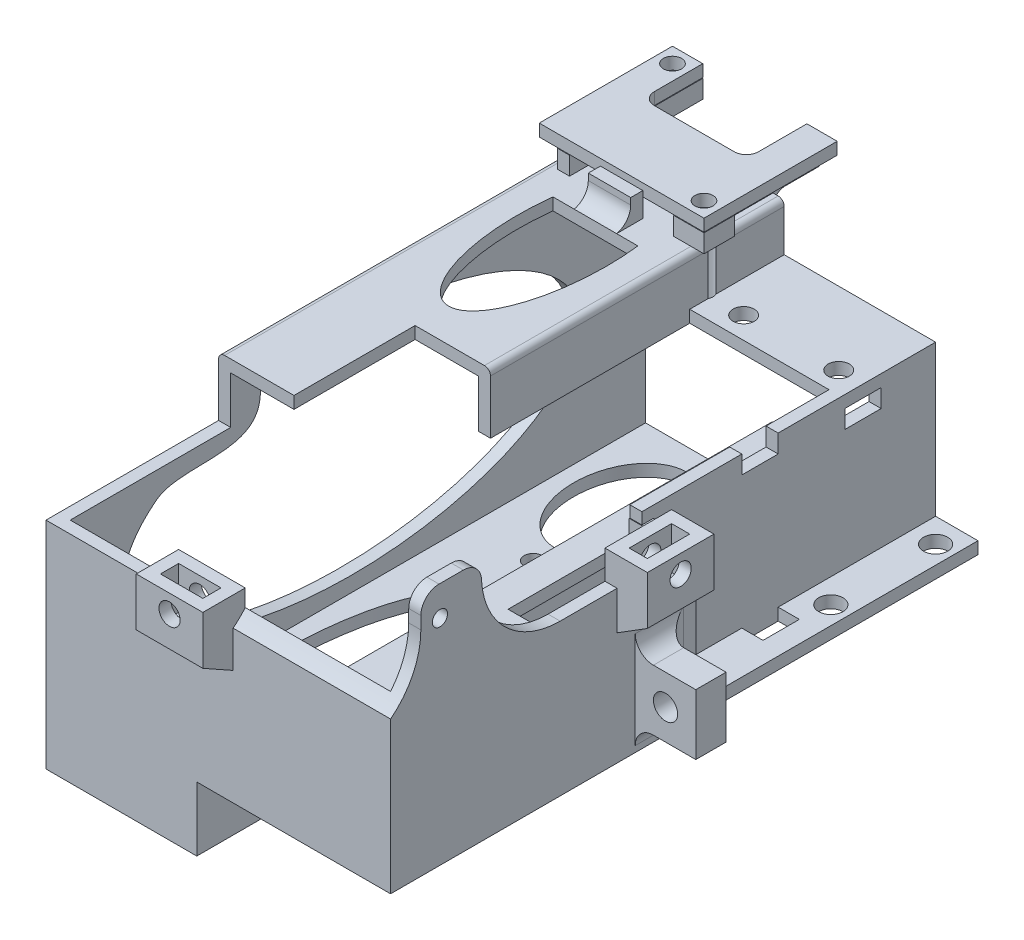
SolidWorks part; units mm, degrees
ref_plane "Front Plane" through (0, 0, 0) normal (0, 0, 1) x (1, 0, 0)
ref_plane "Top Plane" through (0, 0, 0) normal (0, 1, 0) x (1, 0, 0)
ref_plane "Right Plane" through (0, 0, 0) normal (1, 0, 0) x (0, 0, -1)
sketch "Sketch1" plane through (0, 0, 0) normal (0, 1, 0) x (1, 0, 0)
  line L1 (26.45, 47.5) -> (-26.45, 47.5)
  line L2 (26.45, 47.5) -> (26.45, -47.5)
  line L3 (26.45, -47.5) -> (-26.45, -47.5)
  line L4 (-26.45, 47.5) -> (-26.45, -47.5)
  line L5 (26.45, 47.5) -> (-26.45, -47.5) construction
  line L6 (26.45, -47.5) -> (-26.45, 47.5) construction
  point P0 (0, 0)
  dimension "D1" = 52.9
  dimension "D2" = 95
extrude "Boss-Extrude1" add sketch "Sketch1" along normal blind 2
sketch "Sketch2" plane through (0, 2, 0) normal (0, 1, 0) x (1, 0, 0)
  line L0 (-26.45, -47.5) -> (26.45, -47.5)
  line L1 (26.45, -47.5) -> (26.45, 47.5) construction
  line L2 (26.45, -47.5) -> (26.45, -1.1)
  line L3 (26.45, -1.1) -> (19.45, -1.1)
  line L4 (19.45, -1.1) -> (19.45, 47.5)
  line L5 (26.45, 47.5) -> (-26.45, 47.5) construction
  line L6 (19.45, 47.5) -> (-26.45, 47.5) construction
  line L7 (-26.45, 47.5) -> (-26.45, -47.5)
  line L8 (-28.45, 49.5) -> (-28.45, -49.5) construction
  line L9 (-28.45, -49.5) -> (28.45, -49.5)
  line L10 (28.45, -49.5) -> (28.45, 0.9)
  line L11 (28.45, 0.9) -> (21.45, 0.9)
  line L12 (21.45, 0.9) -> (21.45, 49.5) construction
  line L13 (21.45, 49.5) -> (-28.45, 49.5) construction
  line L14 (19.45, 47.5) -> (21.45, 47.5)
  line L15 (-26.45, 47.5) -> (-28.45, 47.5)
  line L16 (-28.45, -49.5) -> (-28.45, 47.5)
  line L17 (21.45, 0.9) -> (21.45, 47.5)
  dimension "D1" = 46.4
  dimension "D2" = 7
  dimension "D3" = 2
extrude "Boss-Extrude2" add sketch "Sketch2" along normal blind 25 from offset 2 offset against normal yes
sketch "Sketch4" plane through (0, 25, 0) normal (0, 1, 0) x (1, 0, 0)
  line L0 (19.45, -1.1) -> (-28.45, -1) construction
  line L1 (-28.45, 47.5) -> (-28.45, -49.5) construction
  line L3 (-28.45, -1) -> (-26.45, -1)
  line L4 (-28.45, -1) -> (-28.45, 47.5)
  line L5 (-28.45, 47.5) -> (-26.45, 47.5)
  line L6 (-26.45, -1) -> (-26.45, 47.5)
extrude "Boss-Extrude3" add sketch "Sketch4" along normal blind 9.8
sketch "Sketch6" plane through (-26.45, 0, 0) normal (1, 0, 0) x (0, 0, -1)
  line L0 (47.5, 34.8) -> (47.5, 2) construction
  line L1 (-1, 34.8) -> (47.5, 34.8)
  line L2 (-1, 34.8) -> (-1, 32.8)
  line L3 (-1, 32.8) -> (47.5, 32.8)
  line L4 (47.5, 34.8) -> (47.5, 32.8)
  dimension "D1" = 2
extrude "Boss-Extrude4" add sketch "Sketch6" along normal blind 22.9
sketch "Sketch7" plane through (0, 32.8, 0) normal (0, -1, 0) x (1, 0, 0)
  line L0 (-3.55, 1) -> (-26.45, 1) construction
  line L1 (-3.55, -47.5) -> (-5.55, -47.5)
  line L2 (-3.55, -47.5) -> (-3.55, 1)
  line L3 (-3.55, 1) -> (-5.55, 1)
  line L4 (-5.55, -47.5) -> (-5.55, 1)
  dimension "D1" = 2
extrude "Boss-Extrude5" add sketch "Sketch7" along normal blind 7.9
sketch "Sketch8" plane through (-3.55, 0, 0) normal (1, 0, 0) x (0, 0, -1)
  line L0 (47.5, 24.9) -> (47.5, 34.8) construction
  line L1 (-1, 24.9) -> (47.5, 24.9)
  line L2 (-1, 24.9) -> (-1, 26.9)
  line L3 (-1, 26.9) -> (47.5, 26.9)
  line L4 (47.5, 24.9) -> (47.5, 26.9)
  dimension "D1" = 2
extrude "Boss-Extrude6" add sketch "Sketch8" along normal up to surface (25 mm away) up to face at (21.45, 13.5, -24.2)
sketch "Sketch9" plane through (0, 0, 1) normal (0, 0, 1) x (1, 0, 0)
  line L0 (-28.45, 25) -> (-26.45, 25)
  line L1 (-26.45, 25) -> (-26.45, 32.8)
  line L2 (-26.45, 32.8) -> (-16, 32.8)
  line L3 (-5.55, 32.8) -> (-26.45, 32.8) construction
  line L4 (-16, 32.8) -> (-16, 34.8)
  line L5 (-28.45, 34.8) -> (-3.55, 34.8) construction
  line L6 (-16, 34.8) -> (-28.45, 34.8)
  line L7 (-28.45, 34.8) -> (-28.45, 25)
extrude "Boss-Extrude7" add sketch "Sketch9" along normal blind 20
sketch "Sketch3" plane through (0, 2, 0) normal (0, 1, 0) x (1, 0, 0)
  line L0 (19.45, -1.1) -> (-26.45, -1.1) construction
  line L2 (-26.45, 47.5) -> (-26.45, -47.5) construction
  line L3 (19.45, -1.1) -> (-0.55, -1.1)
  line L4 (-0.55, -1.1) -> (-0.55, 31.9)
  line L5 (-0.55, 31.9) -> (19.45, 31.9)
  line L6 (19.45, 47.5) -> (19.45, -1.1) construction
  line L7 (19.45, 31.9) -> (19.45, -1.1)
  dimension "D1" = 20
  dimension "D2" = 33
extrude "Cut-Extrude1" cut sketch "Sketch3" against normal mid plane 55
sketch "Sketch62" plane through (-0.55, 0, 0) normal (1, 0, 0) x (0, 0, -1)
  line L1 (-1, 26.9) -> (31.9, 26.9)
  line L2 (-1, 26.9) -> (-1, 24.9)
  line L3 (-1, 24.9) -> (31.9, 24.9)
  line L4 (31.9, 26.9) -> (31.9, 24.9)
extrude "Cut-Extrude25" cut sketch "Sketch62" against normal up to surface (3 mm away) up to face at (-3.55, 30.85, -23.25)
sketch "Sketch13" plane through (0, 25, 0) normal (0, 1, 0) x (1, 0, 0)
  line L0 (28.45, -49.5) -> (28.45, 0.9) construction
  line L1 (26.45, -1.1) -> (28.45, -1.1)
  line L2 (26.45, -1.1) -> (26.45, -12.1)
  line L3 (26.45, -12.1) -> (28.45, -12.1)
  line L4 (28.45, -1.1) -> (28.45, -12.1)
  dimension "D1" = 11
extrude "Boss-Extrude10" add sketch "Sketch13" along normal blind 8 from offset 3.25 offset against normal yes
sketch "Sketch14" plane through (28.45, 0, 0) normal (1, 0, 0) x (0, 0, -1)
  line L1 (-12.1, 29.75) -> (-1.1, 29.75)
  line L2 (-12.1, 29.75) -> (-12.1, 21.75)
  line L3 (-12.1, 21.75) -> (-1.1, 21.75)
  line L4 (-1.1, 29.75) -> (-1.1, 21.75)
  dimension "D1" = 8
extrude "Boss-Extrude11" add sketch "Sketch14" along normal blind 5
sketch "Sketch15" plane through (0, 29.75, 0) normal (0, 1, 0) x (1, 0, 0)
  line L1 (28.45, -10.1) -> (31.45, -10.1)
  line L2 (28.45, -10.1) -> (28.45, -3.1)
  line L3 (28.45, -3.1) -> (31.45, -3.1)
  line L4 (31.45, -10.1) -> (31.45, -3.1)
  line L6 (26.45, -1.1) -> (26.45, -12.1) construction
  line L7 (26.45, -12.1) -> (33.45, -12.1) construction
  line L8 (33.45, -1.1) -> (26.45, -1.1) construction
  dimension "D1" = 2
  dimension "D2" = 3
  dimension "D3" = 2
  dimension "D4" = 2
extrude "Cut-Extrude2" cut sketch "Sketch15" against normal blind 6
sketch "Sketch16" plane through (28.45, 0, 0) normal (1, 0, 0) x (0, 0, -1)
  line L0 (-6.6, 29.75) -> (-6.6, 23.75) construction
  line L1 (-3.1, 29.75) -> (-10.1, 29.75) construction
  line L2 (-3.1, 23.75) -> (-10.1, 23.75) construction
  circle A0 centre (-6.6, 26.75) radius 1.75
  dimension "D1" = 3.5
extrude "Cut-Extrude3" cut sketch "Sketch16" against normal mid plane 15
sketch "Sketch30" plane through (0, 0, 12.1) normal (0, 0, 1) x (1, 0, 0)
  line L0 (33.45, 21.75) -> (26.6464, 17.5043)
rib "Rib8" sketch "Sketch30" sketch "Sketch30" thickness 11 extrusion direction parallel to sketch draft on no parameters "D1"=11
sketch "Sketch37" plane through (0, 23.75, 0) normal (0, 1, 0) x (1, 0, 0)
  line L4 (28.45, -3.1) -> (28.45, -10.1)
  line L5 (28.45, -10.1) -> (31.45, -10.1)
  line L6 (31.45, -10.1) -> (31.45, -3.1)
  line L7 (31.45, -3.1) -> (28.45, -3.1)
  line L8 (28.45, -3.1) -> (28.45, -10.1)
  line L9 (28.45, -10.1) -> (31.45, -10.1)
  line L10 (31.45, -10.1) -> (31.45, -3.1)
  line L11 (31.45, -3.1) -> (28.45, -3.1)
  dimension "D1" = 0
extrude "Cut-Extrude9" cut sketch "Sketch37" against normal blind 1
sketch "Sketch12" plane through (0, 25, 0) normal (0, 1, 0) x (1, 0, 0)
  line L0 (28.45, -49.5) -> (-8.55, -49.5) construction
  line L1 (-28.45, -49.5) -> (28.45, -49.5) construction
  line L2 (26.45, -47.5) -> (-26.45, -47.5) construction
  line L3 (-8.55, -49.5) -> (2.45, -49.5)
  line L4 (-8.55, -49.5) -> (-8.55, -47.5)
  line L5 (-8.55, -47.5) -> (2.45, -47.5)
  line L6 (2.45, -49.5) -> (2.45, -47.5)
  dimension "D1" = 37
  dimension "D2" = 11
extrude "Boss-Extrude9" add sketch "Sketch12" along normal blind 8 from offset 3.25 offset against normal yes
sketch "Sketch18" plane through (0, 0, 49.5) normal (0, 0, 1) x (1, 0, 0)
  line L1 (-8.55, 29.75) -> (2.45, 29.75)
  line L2 (-8.55, 29.75) -> (-8.55, 21.75)
  line L3 (-8.55, 21.75) -> (2.45, 21.75)
  line L4 (2.45, 29.75) -> (2.45, 21.75)
  dimension "D1" = 8
  dimension "D2" = 11
extrude "Boss-Extrude12" add sketch "Sketch18" along normal blind 5
sketch "Sketch20" plane through (0, 29.75, 0) normal (0, 1, 0) x (1, 0, 0)
  line L0 (-3.05, -47.5) -> (-3.05, -54.5) construction
  line L1 (2.45, -47.5) -> (-8.55, -47.5) construction
  line L2 (2.45, -54.5) -> (-8.55, -54.5) construction
  line L3 (2.45, -54.5) -> (2.45, -47.5) construction
  line L4 (0.45, -52.5) -> (-6.55, -52.5)
  line L5 (0.45, -52.5) -> (0.45, -49.5)
  line L6 (0.45, -49.5) -> (-6.55, -49.5)
  line L7 (-6.55, -52.5) -> (-6.55, -49.5)
  line L8 (0.45, -52.5) -> (-6.55, -49.5) construction
  line L9 (0.45, -49.5) -> (-6.55, -52.5) construction
  point P6 (-3.05, -51)
  point P13 (2.45, -51)
  dimension "D1" = 2
  dimension "D2" = 2
extrude "Cut-Extrude4" cut sketch "Sketch20" against normal blind 6
sketch "Sketch21" plane through (0, 0, 49.5) normal (0, 0, 1) x (1, 0, 0)
  line L0 (-3.05, 29.75) -> (-3.05, 23.75) construction
  line L1 (0.45, 29.75) -> (-6.55, 29.75) construction
  line L2 (0.45, 23.75) -> (-6.55, 23.75) construction
  circle A0 centre (-3.05, 26.75) radius 1.75
  dimension "D1" = 3.5
extrude "Cut-Extrude5" cut sketch "Sketch21" against normal mid plane 20
sketch "Sketch29" plane through (-8.55, 0, 0) normal (-1, 0, 0) x (0, 0, 1)
  line L0 (54.5, 21.75) -> (48.2593, 18.2541)
rib "Rib7" sketch "Sketch29" sketch "Sketch29" thickness 11 extrusion direction parallel to sketch draft on no parameters "D1"=11
sketch "Sketch38" plane through (0, 23.75, 0) normal (0, 1, 0) x (1, 0, 0)
  line L4 (-6.55, -49.5) -> (-6.55, -52.5)
  line L5 (-6.55, -52.5) -> (0.45, -52.5)
  line L6 (0.45, -52.5) -> (0.45, -49.5)
  line L7 (0.45, -49.5) -> (-6.55, -49.5)
  line L8 (-6.55, -49.5) -> (-6.55, -52.5)
  line L9 (-6.55, -52.5) -> (0.45, -52.5)
  line L10 (0.45, -52.5) -> (0.45, -49.5)
  line L11 (0.45, -49.5) -> (-6.55, -49.5)
  dimension "D1" = 0
extrude "Cut-Extrude10" cut sketch "Sketch38" against normal blind 1
sketch "Sketch11" plane through (0, 25, 0) normal (0, 1, 0) x (1, 0, 0)
  line L0 (26.45, -12.1) -> (26.45, -47.5) construction
  line L1 (26.45, -44.5) -> (28.45, -44.5)
  line L2 (26.45, -44.5) -> (26.45, -34.5)
  line L3 (26.45, -34.5) -> (28.45, -34.5)
  line L4 (28.45, -44.5) -> (28.45, -34.5)
  line L5 (28.45, -49.5) -> (28.45, -12.1) construction
  line L6 (-28.45, -49.5) -> (-8.55, -49.5) construction
  dimension "D1" = 5
  dimension "D2" = 10
extrude "Boss-Extrude8" add sketch "Sketch11" along normal blind 15.3
sketch "Sketch41" plane through (28.45, 0, 0) normal (1, 0, 0) x (0, 0, -1)
  line L0 (-34.5, 25) -> (-44.5, 25) construction
  line L1 (-40.1, 25) -> (-40.1, 40.3) construction
  line L3 (-44.5, 40.3) -> (-34.5, 40.3) construction
  line L4 (-44.5, 40.3) -> (-44.5, 25) construction
  line L5 (-41.35, 40.3) -> (-41.35, 25) construction
  line L6 (-41.35, 28.25) -> (-41.35, 27) construction
  line L7 (-41.35, 35.35) -> (-41.35, 34.1) construction
  line L8 (-41.35, 28.25) -> (-41.35, 26.8) construction
  circle A1 centre (-41.35, 35.35) radius 1.25
  dimension "D3" = 4.95
  dimension "D1" = 4.4
  dimension "D2" = 1.25
  dimension "D4" = 7.3
extrude "Cut-Extrude11" cut sketch "Sketch41" against normal up to next
fillet "Fillet1" radius 13 1 edges at (27.45, 25, 34.5)
fillet "Fillet2" radius 13 1 edges at (27.45, 25, 44.5)
fillet "Fillet4" radius 3 2 edges at (27.45, 40.3, 44.5) (27.45, 40.3, 34.5)
fillet "Fillet5" radius 1 2 edges at (-28.45, 34.8, -13.25) (-3.55, 34.8, -23.25)
sketch "Sketch42" plane through (0, 26.9, 0) normal (0, 1, 0) x (1, 0, 0)
  line L0 (21.45, 45.5) -> (-3.55, 45.5) construction
  line L1 (21.45, -1) -> (21.45, 47.5) construction
  line L2 (-3.55, 47.5) -> (-3.55, 31.9) construction
  line L3 (21.45, 47.5) -> (-3.55, 47.5) construction
  line L4 (21.45, 43.5) -> (-3.55, 43.5) construction
  line L5 (19.45, 43.5) -> (15.45, 43.5) construction
  line L6 (3.75, 43.5) -> (-0.25, 43.5) construction
  line L7 (17.45, 43.5) -> (17.45, 35.5) construction
  line L8 (1.75, 43.5) -> (1.75, 35.5) construction
  line L9 (17.45, 35.5) -> (1.75, 35.5) construction
  circle A0 centre (17.45, 43.5) radius 2 construction
  circle A1 centre (1.75, 43.5) radius 2 construction
  circle A2 centre (17.45, 35.5) radius 1.75
  circle A3 centre (1.75, 35.5) radius 1.75
  dimension "D6" = 3.5
  dimension "D7" = 3.5
  dimension "D1" = 2
  dimension "D2" = 2
  dimension "D3" = 11.7
  dimension "D4" = 2
  dimension "D5" = 8
extrude "Cut-Extrude12" cut sketch "Sketch42" against normal up to next
sketch "Sketch43" plane through (26.45, 0, 0) normal (1, 0, 0) x (0, 0, -1)
  line L4 (0.9, 2) -> (0.9, 0)
  line L5 (0.9, 0) -> (47.5, 0)
  line L6 (47.5, 0) -> (47.5, 2)
  line L7 (47.5, 2) -> (0.9, 2)
  line L8 (0.9, 2) -> (0.9, 0)
  line L9 (0.9, 0) -> (47.5, 0)
  line L10 (47.5, 0) -> (47.5, 2)
  line L11 (47.5, 2) -> (0.9, 2)
  dimension "D1" = 0
extrude "Boss-Extrude15" add sketch "Sketch43" along normal blind 3
sketch "Sketch48" plane through (0, 2, 0) normal (0, 1, 0) x (1, 0, 0)
  line L0 (26.45, -47.5) -> (10.25, -47.5) construction
  line L1 (-26.45, -47.5) -> (26.45, -47.5) construction
  line L2 (10.25, -47.5) -> (10.25, -32.5) construction
  circle A0 centre (10.25, -32.5) radius 8
  dimension "D3" = 16
  dimension "D1" = 16.2
  dimension "D2" = 15
extrude "Cut-Extrude17" cut sketch "Sketch48" against normal blind 1
sketch "Sketch44" plane through (0, 2, 0) normal (0, 1, 0) x (1, 0, 0)
  line L0 (27.45, 47.5) -> (27.45, 0.9) construction
  line L1 (29.45, 47.5) -> (21.45, 47.5) construction
  line L2 (28.45, 0.9) -> (21.45, 0.9) construction
  line L3 (25.45, 47.5) -> (25.45, 0.9) construction
  line L4 (29.45, 47.5) -> (29.45, 0.9) construction
  line L5 (25.45, 24.2) -> (25.45, 28.2) construction
  line L6 (25.45, 45.5) -> (25.45, 41.5) construction
  circle A0 centre (25.45, 43.5) radius 2
  circle A1 centre (25.45, 26.2) radius 2
  dimension "D1" = 2
  dimension "D2" = 2
  dimension "D3" = 13.3
  dimension "D4" = 2
extrude "Cut-Extrude13" cut sketch "Sketch44" against normal up to next
sketch "Sketch49" plane through (28.45, 0, 0) normal (1, 0, 0) x (0, 0, -1)
  line L0 (-4.1, 9) -> (0.9, 9) construction
  line L2 (0.9, 25) -> (0.9, 2) construction
  line L3 (-4.1, 4) -> (-9.1, 4)
  line L4 (-4.1, 4) -> (-4.1, 14)
  line L5 (-4.1, 14) -> (-9.1, 14)
  line L6 (-9.1, 4) -> (-9.1, 14)
  line L7 (-6.6, 4) -> (-6.6, 0) construction
  line L8 (-49.5, 0) -> (0.9, 0) construction
  dimension "D1" = 5
  dimension "D2" = 10
  dimension "D3" = 5
  dimension "D4" = 4
extrude "Boss-Extrude16" add sketch "Sketch49" along normal blind 10
sketch "Sketch50" plane through (0, 0, 4.1) normal (0, 0, -1) x (-1, 0, 0)
  line L0 (-33.45, 14) -> (-33.45, 4) construction
  line L1 (-38.45, 14) -> (-28.45, 14) construction
  line L2 (-38.45, 4) -> (-28.45, 4) construction
  circle A0 centre (-33.45, 9) radius 2
  dimension "D1" = 4
extrude "Cut-Extrude18" cut sketch "Sketch50" against normal up to next
fillet "Fillet6" radius 3 3 edges at (28.45, 14, 6.6) (28.45, 4, 6.6) (28.45, 9, 4.1)
sketch "Croquis18" plane through (0, 2, 0) normal (0, 1, 0) x (1, 0, 0)
  line L0 (28.45, 0.9) -> (28.45, 47.5)
  line L1 (29.45, 47.5) -> (21.45, 47.5) construction
  line L2 (28.45, 47.5) -> (29.45, 47.5)
  line L3 (29.45, 47.5) -> (29.45, 0.9)
  line L4 (29.45, 0.9) -> (28.45, 0.9)
extrude "cortar-extruir7" cut sketch "Croquis18" against normal through all
sketch "Sketch63" plane through (0, 2, 0) normal (0, 1, 0) x (1, 0, 0)
  line L0 (19.45, 47.5) -> (-26.45, 47.5) construction
  line L1 (-26.45, -47.5) -> (-5.55, -47.5)
  line L2 (-26.45, -47.5) -> (-26.45, 47.5)
  line L3 (-26.45, 47.5) -> (-5.55, 47.5)
  line L4 (-5.55, -47.5) -> (-5.55, 47.5)
  dimension "D1" = 20.9
extrude "Cut-Extrude26" cut sketch "Sketch63" against normal through all
sketch "Sketch64" plane through (0, 0, 0) normal (0, -1, 0) x (1, 0, 0)
  line L0 (-26.45, -47.5) -> (-28.45, -47.5)
  line L1 (-28.45, -47.5) -> (-28.45, 49.5)
  line L2 (-28.45, 49.5) -> (-3.55, 49.5)
  line L3 (-28.45, 49.5) -> (28.45, 49.5) construction
  line L4 (-3.55, 49.5) -> (-3.55, -47.5)
  line L5 (28.45, -47.5) -> (-5.55, -47.5) construction
  line L6 (-3.55, -47.5) -> (-5.55, -47.5)
  line L7 (-5.55, -47.5) -> (-5.55, 47.5)
  line L8 (-5.55, 47.5) -> (-26.45, 47.5)
  line L9 (-26.45, 47.5) -> (-26.45, -47.5)
  dimension "D1" = 2
extrude "Boss-Extrude20" add sketch "Sketch64" along normal blind 10.6
sketch "Sketch65" plane through (0, 0, 47.5) normal (0, 0, -1) x (-1, 0, 0)
  line L0 (26.45, 25) -> (26.45, -10.6) construction
  line L1 (5.55, -10.6) -> (26.45, -10.6)
  line L2 (5.55, -10.6) -> (5.55, -8.6)
  line L3 (5.55, -8.6) -> (26.45, -8.6)
  line L4 (26.45, -10.6) -> (26.45, -8.6)
  dimension "D1" = 2
extrude "Boss-Extrude21" add sketch "Sketch65" along normal up to surface (95 mm away) up to face at (-1.975, 13.6207, -47.5)
sketch "Sketch66" plane through (-28.45, 0, 0) normal (-1, 0, 0) x (0, 0, 1)
  line L0 (-47.5, 11.6) -> (49.5, 11.6) construction
  line L1 (-47.5, 33.8) -> (-47.5, -10.6) construction
  line L2 (49.5, 25) -> (49.5, -10.6) construction
  ellipse E0 centre (1, 11.6) end of major axis (38.6876, 11.6) minor radius 17.7076 (16.1001, 27.8242) -> (33.3321, 20.6986) ccw
  spline S0 degree 3 poles (16.1001, 27.8242) (15.9403, 18.9184) (29.0114, 24.0621) (33.3321, 20.6986) knots 0 0 0 0 1 1 1 1
extrude "Cut-Extrude29" cut sketch "Sketch66" against normal blind 10.6
sketch "Sketch67" plane through (0, -10.6, 0) normal (0, -1, 0) x (1, 0, 0)
  line L0 (-28.45, 49.5) -> (-28.45, -18.5) construction
  line L1 (-28.45, 49.5) -> (-28.45, -47.5) construction
  line L2 (-28.45, -18.5) -> (-3.55, -18.5) construction
  line L3 (-3.55, -47.5) -> (-3.55, 49.5) construction
  line L4 (-3.55, -18.5) -> (-16, -18.5) construction
  line L5 (-16, -18.5) -> (-16, 49.5) construction
  line L6 (-3.55, 49.5) -> (-28.45, 49.5) construction
  line L7 (-16, -18.5) -> (-16, -47.5) construction
  line L8 (-28.45, -47.5) -> (-3.55, -47.5) construction
  ellipse E0 centre (-16, 15.5) end of major axis (-16, -8.2417) minor radius 7.8282
  ellipse E1 centre (-16, -33) end of major axis (-16, -43.8649) minor radius 7.8282
  dimension "D1" = 68
extrude "Cut-Extrude30" cut sketch "Sketch67" against normal up to next
sketch "Sketch53" plane through (0, 2, 0) normal (0, 1, 0) x (1, 0, 0)
  line L0 (21.45, 0.9) -> (21.45, 47.5) construction
  line L1 (21.45, 15.5) -> (24.95, 15.5)
  line L2 (21.45, 15.5) -> (21.45, 21.5)
  line L3 (21.45, 21.5) -> (24.95, 21.5)
  line L4 (24.95, 15.5) -> (24.95, 21.5)
  line L5 (28.45, 47.5) -> (21.45, 47.5) construction
  dimension "D1" = 26
  dimension "D2" = 6
  dimension "D3" = 3.5
extrude "Cut-Extrude21" cut sketch "Sketch53" against normal up to next
sketch "Sketch69" plane through (21.45, 0, 0) normal (1, 0, 0) x (0, 0, -1)
  line L0 (15.5, 2) -> (21.5, 2) construction
  line L1 (21.5, 2) -> (18.5, 2) construction
  line L2 (18.5, 2) -> (18.5, 26.9) construction
  line L3 (-1, 26.9) -> (47.5, 26.9) construction
  line L5 (21.5, 29.9) -> (15.5, 29.9)
  line L6 (21.5, 29.9) -> (21.5, 23.9)
  line L7 (21.5, 23.9) -> (15.5, 23.9)
  line L8 (15.5, 29.9) -> (15.5, 23.9)
  line L9 (21.5, 29.9) -> (15.5, 23.9) construction
  line L10 (21.5, 23.9) -> (15.5, 29.9) construction
  dimension "D1" = 6
  dimension "D2" = 6
extrude "Cut-Extrude31" cut sketch "Sketch69" against normal up to next
sketch "Sketch70" plane through (21.45, 0, 0) normal (1, 0, 0) x (0, 0, -1)
  line L1 (0.9, 2) -> (6.9, 2)
  line L2 (0.9, 2) -> (0.9, 6)
  line L3 (0.9, 6) -> (6.9, 6)
  line L4 (6.9, 2) -> (6.9, 6)
  dimension "D1" = 6
  dimension "D2" = 4
extrude "Cut-Extrude32" cut sketch "Sketch70" against normal up to next
sketch "Sketch71" plane through (19.45, 0, 0) normal (-1, 0, 0) x (0, 0, 1)
  line L0 (-35.5, 24.9) -> (-35.5, 21.9) construction
  line L2 (-32.5, 21.9) -> (-38.5, 21.9)
  line L3 (-32.5, 21.9) -> (-32.5, 24.9)
  line L4 (-32.5, 24.9) -> (-38.5, 24.9)
  line L5 (-38.5, 21.9) -> (-38.5, 24.9)
  line L6 (-32.5, 21.9) -> (-38.5, 24.9) construction
  line L7 (-32.5, 24.9) -> (-38.5, 21.9) construction
  line L9 (-21.5, 26.9) -> (-47.5, 26.9) construction
  line L10 (-47.5, 26.9) -> (-47.5, 2) construction
  point P3 (-35.5, 23.4)
  point P10 (0, 0)
  point P12 (0, 0)
  point P14 (0, 0)
  dimension "D1" = 3
  dimension "D2" = 6
  dimension "D3" = 2
  dimension "D4" = 9
extrude "Cut-Extrude33" cut sketch "Sketch71" against normal up to next
sketch "Sketch73" plane through (0, -10.6, 0) normal (0, -1, 0) x (1, 0, 0)
  line L0 (-28.45, 49.5) -> (-28.45, -18.5) construction
  line L1 (-28.45, 49.5) -> (-28.45, -47.5) construction
  line L2 (-28.45, -18.5) -> (-3.55, -18.5) construction
  line L3 (-3.55, -47.5) -> (-3.55, 49.5) construction
  circle A0 centre (-16, -18.5) radius 1.5
  dimension "D2" = 3
  dimension "D1" = 68
extrude "Cut-Extrude34" cut sketch "Sketch73" against normal up to next
sketch "Sketch74" plane through (0, 34.8, 0) normal (0, 1, 0) x (1, 0, 0)
  line L0 (-16, 47.5) -> (-16, -1) construction
  line L1 (-4.55, 47.5) -> (-27.45, 47.5) construction
  ellipse E0 centre (-16, 23.25) end of major axis (-16, 41.9586) minor radius 7.3358
extrude "Cut-Extrude35" cut sketch "Sketch74" against normal up to next
sketch "Sketch75" plane through (0, 34.8, 0) normal (0, 1, 0) x (1, 0, 0)
  line L0 (-27.45, 47.5) -> (-16, 47.5) construction
  line L1 (-4.55, 47.5) -> (-27.45, 47.5) construction
  line L2 (-16, 47.5) -> (-16, 55.1) construction
  line L3 (-24.6, 55.1) -> (-7.4, 55.1) construction
  line L4 (-24.6, 55.1) -> (-24.6, 33.1)
  line L5 (-7.4, 55.1) -> (-7.4, 33.1)
  line L6 (-7.4, 33.1) -> (-24.6, 33.1) construction
  line L7 (-26.6, 57.1) -> (-26.6, 31.1) construction
  line L8 (-5.4, 31.1) -> (-26.6, 31.1) construction
  line L9 (-5.4, 57.1) -> (-5.4, 31.1) construction
  line L10 (-26.6, 57.1) -> (-5.4, 57.1) construction
  line L11 (-24.6, 55.1) -> (-26.6, 55.1)
  line L12 (-26.6, 55.1) -> (-26.6, 33.1)
  line L13 (-26.6, 33.1) -> (-24.6, 33.1)
  line L14 (-7.4, 55.1) -> (-5.4, 55.1)
  line L15 (-5.4, 55.1) -> (-5.4, 33.1)
  line L16 (-5.4, 33.1) -> (-7.4, 33.1)
  point P8 (-16, 55.1)
  dimension "D1" = 11.45
  dimension "D2" = 7.6
  dimension "D3" = 22
  dimension "D5" = 17.2
  dimension "D4" = 2
sketch "Sketch76" plane through (0, 34.8, 0) normal (0, 1, 0) x (1, 0, 0)
  line L0 (-4.55, -1) -> (-4.55, 47.5) construction
  line L1 (-27.45, 47.5) -> (-4.55, 47.5)
  line L2 (-27.45, 47.5) -> (-27.45, 28.7766)
  line L3 (-27.45, 28.7766) -> (-4.55, 28.7766)
  line L4 (-4.55, 47.5) -> (-4.55, 28.7766)
extrude "Boss-Extrude22" add sketch "Sketch76" against normal blind 2
extrude "Boss-Extrude23" add sketch "Sketch75" along normal blind 3
sketch "Sketch77" plane through (0, 34.8, 0) normal (0, 1, 0) x (1, 0, 0)
  line L0 (-24.6, 33.1) -> (-7.4, 33.1) construction
  line L1 (-12.5, 33.1) -> (-19.5, 33.1)
  line L2 (-19.5, 33.1) -> (-19.5, 31.1)
  line L3 (-19.5, 31.1) -> (-12.5, 31.1)
  line L4 (-12.5, 31.1) -> (-12.5, 33.1)
  point P7 (-16, 33.1)
  dimension "D1" = 7
  dimension "D2" = 2
extrude "Boss-Extrude24" add sketch "Sketch77" along normal blind 4
fillet "Fillet7" radius 3 1 edges at (-16, 34.8, -31.1)
fillet "Fillet8" radius 2 2 edges at (-25.6, 34.8, -47.5) (-6.4, 34.8, -47.5)
sketch "Sketch78" plane through (-26.6, 0, 0) normal (-1, 0, 0) x (0, 0, 1)
  line L0 (-55.1, 34.8) -> (-49.5, 34.8) construction
  line L1 (-55.1, 37.8) -> (-50.1, 37.8)
  line L2 (-55.1, 37.8) -> (-55.1, 34.8)
  line L3 (-55.1, 34.8) -> (-50.1, 34.8)
  line L4 (-50.1, 37.8) -> (-50.1, 34.8)
  dimension "D1" = 5
extrude "Boss-Extrude25" add sketch "Sketch78" along normal blind 3
sketch "Sketch80" plane through (-5.4, 0, 0) normal (1, 0, 0) x (0, 0, -1)
  line L0 (49.5, 34.8) -> (55.1, 34.8) construction
  line L1 (33.1, 37.8) -> (38.1, 37.8)
  line L2 (33.1, 37.8) -> (33.1, 34.8)
  line L3 (33.1, 34.8) -> (38.1, 34.8)
  line L4 (38.1, 37.8) -> (38.1, 34.8)
  dimension "D1" = 5
extrude "Boss-Extrude27" add sketch "Sketch80" along normal blind 3
sketch "Sketch81" plane through (0, 37.8, 0) normal (0, 1, 0) x (1, 0, 0)
  line L0 (-29.6, 52.6) -> (-24.6, 52.6) construction
  line L1 (-29.6, 50.1) -> (-29.6, 55.1) construction
  line L2 (-24.6, 33.1) -> (-24.6, 55.1) construction
  line L3 (-2.4, 35.6) -> (-7.4, 35.6) construction
  line L4 (-2.4, 38.1) -> (-2.4, 33.1) construction
  line L5 (-7.4, 55.1) -> (-7.4, 33.1) construction
  circle A0 centre (-27.1, 52.6) radius 1.5
  circle A1 centre (-4.9, 35.6) radius 1.5
  dimension "D1" = 3
  dimension "D2" = 3
extrude "Cut-Extrude36" cut sketch "Sketch81" against normal up to next
surface "Surface-Offset1" parameters "D1"=0.1
sketch "Sketch83" plane through (0, 37.9, 0) normal (0, 1, 0) x (1, 0, 0)
  line L0 (-2.4, 55.1) -> (-7.4, 55.1)
  line L1 (-29.6, 55.1) -> (-2.4, 55.1) construction
  line L2 (-29.6, 55.1) -> (-29.6, 33.1)
  line L3 (-29.6, 33.1) -> (-2.4, 33.1)
  line L4 (-2.4, 55.1) -> (-2.4, 33.1)
  line L5 (-7.4, 55.1) -> (-7.4, 45.1)
  line L6 (-7.4, 55.1) -> (-7.4, 33.1) construction
  line L7 (-7.4, 45.1) -> (-24.6, 45.1)
  line L8 (-24.6, 33.1) -> (-24.6, 55.1) construction
  line L9 (-24.6, 45.1) -> (-24.6, 55.1)
  line L10 (-24.6, 55.1) -> (-29.6, 55.1)
  circle A0 centre (-27.1, 52.6) radius 1.5
  circle A1 centre (-4.9, 35.6) radius 1.5
  dimension "D1" = 3
  dimension "D2" = 3
  dimension "D3" = 10
extrude "Boss-Extrude28" add sketch "Sketch83" along normal blind 2 separate body
fillet "Fillet9" radius 2 2 edges at (-24.6, 38.9, -45.1) (-7.4, 38.9, -45.1)
sketch "Sketch84" plane through (0, 0, -47.5) normal (0, 0, -1) x (-1, 0, 0)
  line L1 (33.6936, 32.8) -> (0, 32.8)
  line L2 (33.6936, 32.8) -> (33.6936, 46.6768)
  line L3 (33.6936, 46.6768) -> (0, 46.6768)
  line L4 (0, 32.8) -> (0, 46.6768)
extrude "Cut-Extrude37" [suppressed] cut sketch "Sketch84" against normal mid plane 300 flip side to cut
sketch "Sketch85" plane through (0, 34.8, 0) normal (0, 1, 0) x (1, 0, 0)
  line L1 (5.7683, 28.6367) -> (-44.2543, 28.6367)
  line L2 (5.7683, 28.6367) -> (5.7683, -31.3076)
  line L3 (5.7683, -31.3076) -> (-44.2543, -31.3076)
  line L4 (-44.2543, 28.6367) -> (-44.2543, -31.3076)
extrude "Cut-Extrude39" [suppressed] cut sketch "Sketch85" against normal blind 40
